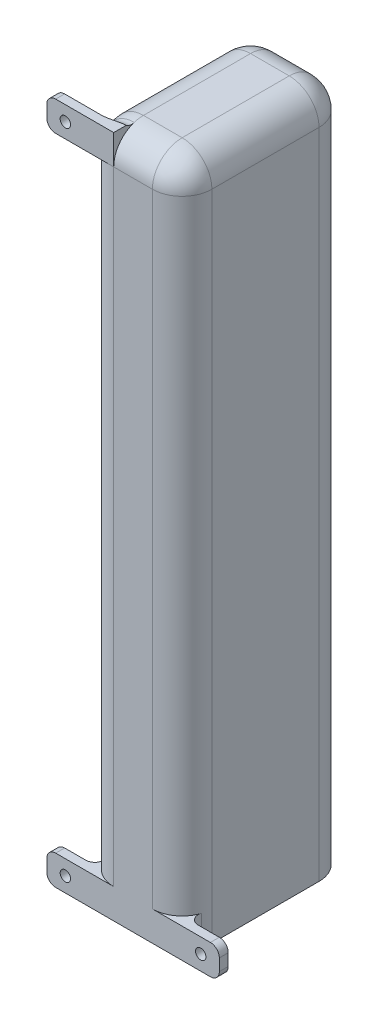
SolidWorks part; units mm, degrees
ref_plane "Plan de face" through (0, 0, 0) normal (0, 0, 1) x (1, 0, 0)
ref_plane "Plan de dessus" through (0, 0, 0) normal (0, 1, 0) x (1, 0, 0)
ref_plane "Plan de droite" through (0, 0, 0) normal (1, 0, 0) x (0, 0, -1)
sketch "Esquisse1" plane through (0, 0, 0) normal (0, 1, 0) x (1, 0, 0)
  line L3 (16.5, 28) -> (-16.5, 28)
  line L4 (13.5, -25) -> (-13.5, -25)
  line L5 (13.5, -25) -> (13.5, 25)
  line L6 (13.5, 25) -> (-13.5, 25)
  line L7 (-13.5, -25) -> (-13.5, 25)
  line L8 (13.5, -25) -> (-13.5, 25) construction
  line L9 (13.5, 25) -> (-13.5, -25) construction
  line L10 (-16.5, -28) -> (-16.5, 28)
  line L11 (16.5, -28) -> (-16.5, -28)
  line L12 (16.5, -28) -> (16.5, 28)
  point P10 (0, 0)
  dimension "D3" = 27
  dimension "D4" = 50
  dimension "D5" = 3
extrude "Boss.-Extru.1" add sketch "Esquisse1" along normal blind 226.5
sketch "Esquisse2" plane through (0, 226.5, 0) normal (0, 1, 0) x (1, 0, 0)
  line L5 (13.5, 25) -> (-13.5, 25) construction
  line L6 (-16.5, 28) -> (16.5, 28)
  line L8 (-16.5, 28) -> (-16.5, -28)
  line L9 (-16.5, -28) -> (16.5, -28)
  line L10 (16.5, 28) -> (16.5, -28)
  line L11 (0, 25) -> (0, 28) construction
  line L12 (-13.5, 0) -> (-16.5, 0) construction
  line L13 (-13.5, -25) -> (-13.5, 25) construction
  point P4 (0, -28)
  point P5 (-16.5, 0)
  dimension "D1" = 3
extrude "Boss.-Extru.2" add sketch "Esquisse2" along normal blind 3
fillet "Congé1" radius 10 8 edges at (16.5, 114.75, 28) (-16.5, 114.75, 28) (16.5, 114.75, -28) (-16.5, 114.75, -28) (0, 229.5, -28) (16.5, 229.5, 0) (0, 229.5, 28) (-16.5, 229.5, 0)
sketch "Esquisse3" plane through (0, 0, 28) normal (0, 0, 1) x (1, 0, 0)
  line L0 (-29, 224.5) -> (-16.5, 224.5) construction
  line L1 (-6.5, 229.5) -> (-29, 229.5)
  line L2 (-6.5, 229.5) -> (-6.5, 219.5)
  line L3 (-6.5, 219.5) -> (-29, 219.5)
  line L4 (-29, 229.5) -> (-29, 219.5)
  line L6 (0, 229.5) -> (0, 0) construction
  line L8 (16.5, 114.75) -> (-16.5, 114.75) construction
  line L10 (29, 229.5) -> (29, 219.5) construction
  line L11 (6.5, 229.5) -> (29, 229.5) construction
  line L12 (6.5, 229.5) -> (6.5, 219.5) construction
  line L13 (6.5, 219.5) -> (29, 219.5) construction
  line L14 (6.5, 10) -> (29, 10)
  line L15 (6.5, 0) -> (6.5, 10)
  line L16 (6.5, 0) -> (29, 0)
  line L17 (29, 0) -> (29, 10)
  line L18 (-6.5, 0) -> (-6.5, 10)
  line L19 (-6.5, 0) -> (-29, 0)
  line L20 (-29, 0) -> (-29, 10)
  line L21 (-6.5, 10) -> (-29, 10)
  line L22 (-6.5, 219.5) -> (-6.5, 0) construction
  line L27 (-16.5, 0) -> (-16.5, 219.5) construction
  line L28 (-16.5, 229.5) -> (16.5, 229.5) construction
  line L29 (16.5, 219.5) -> (16.5, 0) construction
  circle A0 centre (-22.75, 224.5) radius 1.75
  circle A1 centre (22.75, 224.5) radius 1.75 construction
  circle A2 centre (22.75, 5) radius 1.75
  circle A3 centre (-22.75, 5) radius 1.75
  point P6 (0, 114.75)
  dimension "D1" = 3.5
  dimension "D2" = 10
  dimension "D3" = 12.5
extrude "Boss.-Extru.3" add sketch "Esquisse3" against normal blind 3
fillet "Congé3" radius 7 8 edges at (0, 226.5, -25) (-13.5, 226.5, 0) (0, 226.5, 25) (13.5, 226.5, 0) (-13.5, 113.25, 25) (13.5, 113.25, -25) (-13.5, 113.25, -25) (13.5, 113.25, 25)
fillet "Congé6" radius 3 9 edges at (-11.5498, 224.5498, 25) (-13.6414, 5, 25) (13.6414, 5, 25) (29, 0, 26.5) (29, 10, 26.5) (-29, 0, 26.5) (-29, 10, 26.5) (-29, 219.5, 26.5) (-29, 229.5, 26.5)
